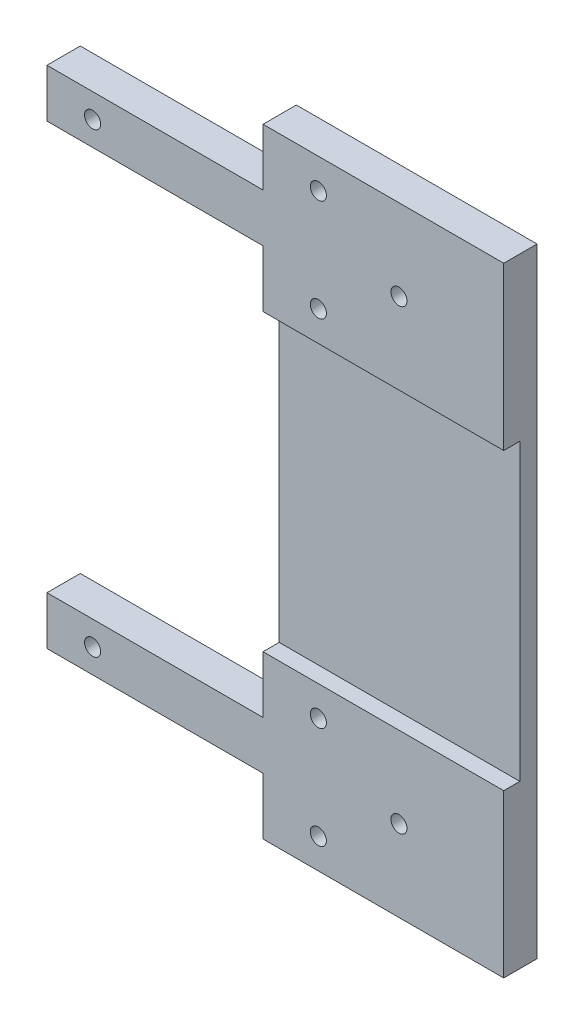
SolidWorks part; units mm, degrees
ref_plane "Plano frontal" through (0, 0, 0) normal (0, 0, 1) x (1, 0, 0)
ref_plane "Plano superior" through (0, 0, 0) normal (0, 1, 0) x (1, 0, 0)
ref_plane "Plano direito" through (0, 0, 0) normal (1, 0, 0) x (0, 0, -1)
sketch "Esboço1" plane through (0, 0, 0) normal (0, 0, 1) x (1, 0, 0)
  line L0 (-35.4466, -13.1045) -> (-26.9466, -13.1045) construction
  line L1 (4.7645, 16.9889) -> (49.5534, 16.9889)
  line L2 (4.7645, 6.3955) -> (-35.4466, 6.3955)
  line L3 (4.7645, -13.1979) -> (49.5534, -13.1979)
  line L4 (49.5534, 16.9889) -> (49.5534, -13.1979)
  line L5 (-26.9466, -13.1045) -> (30.0534, -13.1045) construction
  line L6 (-35.4466, 1.8955) -> (49.5534, 1.8955) construction
  line L7 (30.0534, 1.8955) -> (15.0534, 1.8955) construction
  line L8 (15.0534, 1.8955) -> (15.0534, 11.3955) construction
  line L9 (15.0534, 1.8955) -> (15.0534, -7.6045) construction
  line L10 (4.7645, 16.9889) -> (4.7645, 6.3955)
  line L11 (-35.4466, 6.3955) -> (-35.4466, -2.6045)
  line L12 (4.7645, -13.1979) -> (4.7645, -2.6045)
  line L13 (-35.4466, -2.6045) -> (4.7645, -2.6045)
  line L14 (30.0534, 1.8955) -> (30.0534, 86.8955) construction
  line L15 (30.0534, 44.3955) -> (-70.9471, 44.3955) construction
  line L16 (15.0534, 86.8955) -> (15.0534, 96.3955) construction
  line L17 (15.0534, 86.8955) -> (15.0534, 77.3955) construction
  line L18 (30.0534, 86.8955) -> (15.0534, 86.8955) construction
  line L19 (-35.4466, 86.8955) -> (49.5534, 86.8955) construction
  line L20 (-26.9466, 101.8955) -> (30.0534, 101.8955) construction
  line L21 (-35.4466, 101.8955) -> (-26.9466, 101.8955) construction
  line L22 (-35.4466, 91.3955) -> (4.7645, 91.3955)
  line L23 (4.7645, 101.9889) -> (4.7645, 91.3955)
  line L24 (-35.4466, 82.3955) -> (-35.4466, 91.3955)
  line L25 (4.7645, 71.8021) -> (4.7645, 82.3955)
  line L26 (49.5534, 71.8021) -> (49.5534, 101.9889)
  line L27 (4.7645, 101.9889) -> (49.5534, 101.9889)
  line L28 (4.7645, 82.3955) -> (-35.4466, 82.3955)
  line L29 (4.7645, 71.8021) -> (49.5534, 71.8021)
  line L30 (4.7645, 71.8021) -> (4.7645, 16.9889)
  line L35 (49.5534, 71.8021) -> (49.5534, 16.9889)
  circle A0 centre (-26.9466, 1.8955) radius 1.5
  circle A1 centre (30.0534, 1.8955) radius 1.5
  circle A2 centre (15.0534, 11.3955) radius 1.5
  circle A3 centre (15.0534, -7.6045) radius 1.5
  circle A4 centre (15.0534, 96.3955) radius 1.5
  circle A5 centre (15.0534, 77.3955) radius 1.5
  circle A6 centre (30.0534, 86.8955) radius 1.5
  circle A7 centre (-26.9466, 86.8955) radius 1.5
extrude "Ressalto-extrusão3" add sketch "Esboço1" along normal blind 6.2 contours L25 L29 L26 L27 L23 L22 L24 L28 A6 A4 A5 A7 | L11 L13 L12 L3 L4 L1 L10 L2 A3 A2 A1 A0 region at (18.3507, 1.8955, 0) region at (18.3507, 86.8955, 0)
extrude "Ressalto-extrusão4" add sketch "Esboço1<7>" along normal blind 3.2 contours L35 L29 L30 L1 region at (27.1589, 44.3955, 0)
sketch "Esboço1<7>" plane through (0, 0, 0) normal (0, 0, 1) x (1, 0, 0) same geometry as "Esboço1"
